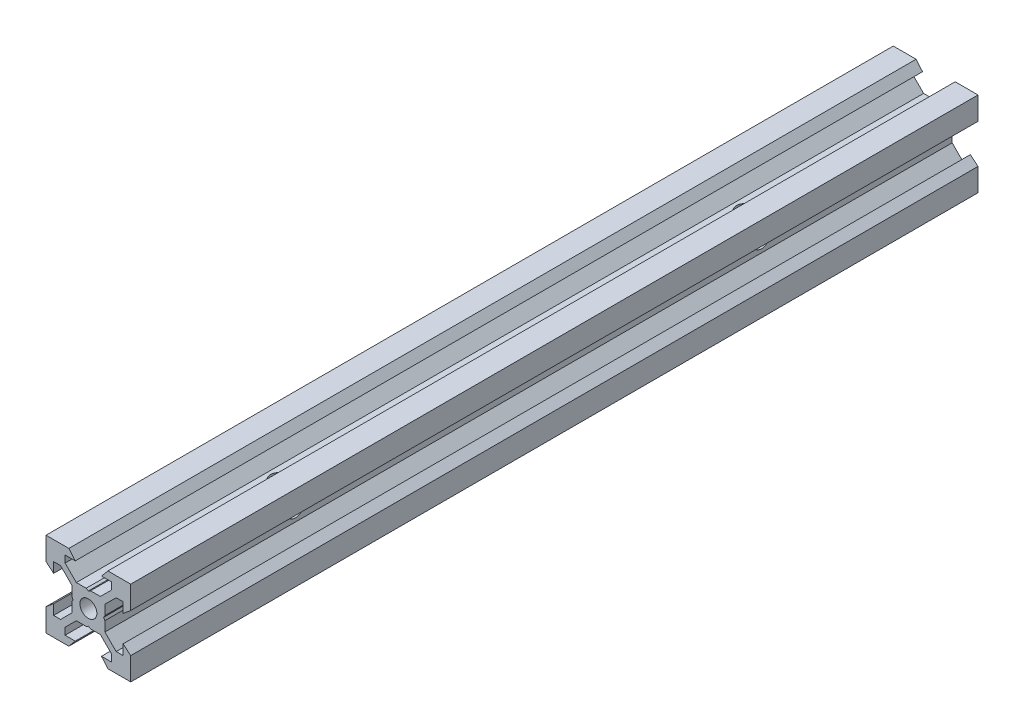
SolidWorks part; units mm, degrees
material "3.3535 (EN-AW 5754)"
ref_plane "Front Plane" through (0, 0, 0) normal (0, 0, 1) x (1, 0, 0)
ref_plane "Top Plane" through (0, 0, 0) normal (0, 1, 0) x (1, 0, 0)
ref_plane "Right Plane" through (0, 0, 0) normal (1, 0, 0) x (0, 0, -1)
sketch "Sketch1" plane through (0, 0, 0) normal (0, 0, 1) x (1, 0, 0)
  line L0 (10, 10) -> (4.6104, 10) construction
  line L1 (10, 10) -> (10, 4.6104) construction
  line L2 (10, -10) -> (10, -4.6104) construction
  line L3 (10, -10) -> (4.6104, -10) construction
  line L4 (10, 10) -> (10, 4.6104)
  line L5 (6.5607, 5.5) -> (8.2, 5.5)
  line L6 (5.5, 8.2) -> (5.5, 6.5607)
  line L7 (10, 10) -> (4.6104, 10)
  line L8 (10, 10) -> (10, 4.6104)
  line L9 (6.5607, 5.5) -> (3.9, 2.8393)
  line L10 (5.5, 6.5607) -> (2.8393, 3.9)
  line L11 (10, 4.6104) -> (8.2, 3.1)
  line L12 (4.6104, 10) -> (3.1, 8.2)
  line L13 (8.2, 3.1) -> (8.2, 5.5)
  line L14 (3.1, 8.2) -> (5.5, 8.2)
  line L15 (-6.5607, 5.5) -> (-8.2, 5.5)
  line L16 (6.5607, -5.5) -> (8.2, -5.5)
  line L17 (3.1, -8.2) -> (5.5, -8.2)
  line L18 (8.2, -3.1) -> (8.2, -5.5)
  line L19 (4.6104, -10) -> (3.1, -8.2)
  line L20 (10, -4.6104) -> (8.2, -3.1)
  line L21 (0.5196, -3.9) -> (0, -3.6)
  line L22 (0.5196, 3.9) -> (0, 3.6)
  line L23 (3.6, 0) -> (3.9, -0.5196)
  line L24 (3.9, 0.5196) -> (3.6, 0)
  line L25 (3.9, 0.5196) -> (3.9, 2.8393)
  line L26 (2.8393, 3.9) -> (0.5196, 3.9)
  line L27 (3.9, -2.8393) -> (3.9, -0.5196)
  line L28 (2.8393, -3.9) -> (0.5196, -3.9)
  line L29 (5.5, -6.5607) -> (2.8393, -3.9)
  line L30 (6.5607, -5.5) -> (3.9, -2.8393)
  line L31 (10, -10) -> (10, -4.6104)
  line L32 (10, -10) -> (4.6104, -10)
  line L33 (5.5, -8.2) -> (5.5, -6.5607)
  line L34 (-6.5607, -5.5) -> (-8.2, -5.5)
  line L35 (10, -10) -> (10, -4.6104)
  line L36 (0, 0) -> (0, 8.2) construction
  line L37 (-10, -10) -> (-4.6104, -10) construction
  line L38 (-10, -10) -> (-10, -4.6104) construction
  line L39 (-10, 10) -> (-10, 4.6104) construction
  line L40 (-10, 10) -> (-4.6104, 10) construction
  line L41 (-10, -10) -> (-10, -4.6104)
  line L43 (-5.5, -8.2) -> (-5.5, -6.5607)
  line L44 (-10, -10) -> (-4.6104, -10)
  line L45 (-10, -10) -> (-10, -4.6104)
  line L46 (-6.5607, -5.5) -> (-3.9, -2.8393)
  line L47 (-5.5, -6.5607) -> (-2.8393, -3.9)
  line L48 (-2.8393, -3.9) -> (-0.5196, -3.9)
  line L49 (-3.9, -2.8393) -> (-3.9, -0.5196)
  line L50 (-2.8393, 3.9) -> (-0.5196, 3.9)
  line L51 (-3.9, 0.5196) -> (-3.9, 2.8393)
  line L52 (-3.9, 0.5196) -> (-3.6, 0)
  line L53 (-3.6, 0) -> (-3.9, -0.5196)
  line L54 (-0.5196, 3.9) -> (0, 3.6)
  line L55 (-0.5196, -3.9) -> (0, -3.6)
  line L56 (-10, -4.6104) -> (-8.2, -3.1)
  line L57 (-4.6104, -10) -> (-3.1, -8.2)
  line L58 (-8.2, -3.1) -> (-8.2, -5.5)
  line L59 (-3.1, -8.2) -> (-5.5, -8.2)
  line L60 (-10, -10) -> (10, -10) construction
  line L61 (-10, -10) -> (-10, 10) construction
  line L62 (-3.1, 8.2) -> (-5.5, 8.2)
  line L63 (-8.2, 3.1) -> (-8.2, 5.5)
  line L64 (-4.6104, 10) -> (-3.1, 8.2)
  line L65 (-10, 4.6104) -> (-8.2, 3.1)
  line L66 (-5.5, 6.5607) -> (-2.8393, 3.9)
  line L67 (-6.5607, 5.5) -> (-3.9, 2.8393)
  line L68 (-10, 10) -> (-10, 4.6104)
  line L69 (-10, 10) -> (-4.6104, 10)
  line L70 (-5.5, 8.2) -> (-5.5, 6.5607)
  line L71 (-10, 10) -> (10, 10) construction
  line L72 (-10, 10) -> (-10, 4.6104)
  line L73 (10, -10) -> (10, 10) construction
  line L74 (-10, -10) -> (10, 10) construction
  line L75 (-10, 10) -> (10, -10) construction
  circle A0 centre (0, 0) radius 2
  dimension "D7" = 4
  dimension "D1" = 20
  dimension "D2" = 5.3896
  dimension "D3" = 4.5
  dimension "D4" = 50
  dimension "D5" = 1.8
  dimension "D6" = 1.5104
  dimension "D8" = 5.5
  dimension "D9" = 120
  dimension "D10" = 0.3
  dimension "D11" = 2.3197
  dimension "D12" = 7.8
  dimension "D13" = 7.8
  dimension "D14" = 1.5
  dimension "D15" = 2.6607
extrude "Boss-Extrude1" add sketch "Sketch1" along normal blind 200 contours L70 L62 L64 L69 L68 L65 L63 L15 L67 L51 L52 L53 L49 L46 L34 L58 L56 L41 L44 L57 L59 L43 L47 L48 L55 L21 L28 L29 L33 L17 L19 L32 L31 L20 L18 L16 L30 L27 L23 L24 L25 L9 L5 L13 L11 L4 L7 L12 L14 L6 L10 region at (9.7172, 7.3052, 0)
sketch "Sketch2" plane through (0, -3.9, 0) normal (0, -1, 0) x (-1, 0, 0)
  line L0 (0, -200) -> (0, -155) construction
  line L1 (0, -200) -> (0, 0) construction
  line L2 (0, 0) -> (0, -45) construction
  circle A0 centre (0, -155) radius 2
  circle A1 centre (0, -45) radius 2
  dimension "D2" = 4
  dimension "D4" = 4
  dimension "D1" = 45
  dimension "D3" = 45
extrude "Cut-Extrude1" cut sketch "Sketch2" against normal through all both and the other way through all
sketch "Sketch3" plane through (3.9, 0, 0) normal (1, 0, 0) x (0, 0, -1)
  line L0 (0, 0) -> (-45, 0) construction
  line L1 (-200, 0) -> (0, 0) construction
  line L2 (-200, 0) -> (-155, 0) construction
  circle A0 centre (-45, 0) radius 2
  circle A1 centre (-155, 0) radius 2
  dimension "D2" = 4
  dimension "D4" = 4
  dimension "D1" = 45
  dimension "D3" = 45
extrude "Cut-Extrude2" cut sketch "Sketch3" against normal through all both
